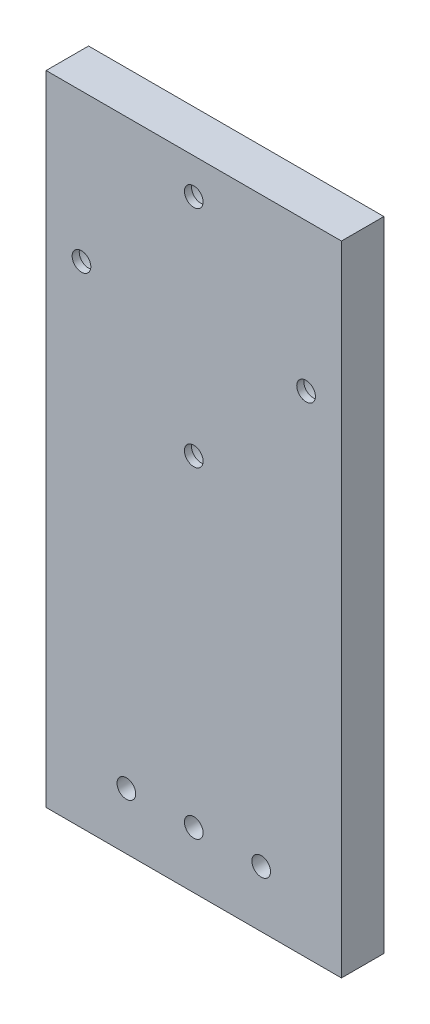
SolidWorks part; units mm, degrees
ref_plane "Front Plane" through (0, 0, 0) normal (0, 0, 1) x (1, 0, 0)
ref_plane "Top Plane" through (0, 0, 0) normal (0, 1, 0) x (1, 0, 0)
ref_plane "Right Plane" through (0, 0, 0) normal (1, 0, 0) x (0, 0, -1)
sketch "Sketch1" plane through (0, 0, 0) normal (0, 0, 1) x (1, 0, 0)
  line L0 (0, 0) -> (50000, 0) construction
  line L1 (0, 0) -> (0, -50000) construction
  line L2 (-9.53, -61.35) -> (49990.47, -61.35) construction
  line L4 (-20.875, 20.875) -> (20.875, 20.875)
  line L5 (-20.875, 20.875) -> (-20.875, -69.35)
  line L6 (-20.875, -69.35) -> (20.875, -69.35)
  line L7 (20.875, 20.875) -> (20.875, -69.35)
  line L13 (0, 9.53) -> (0, -4.4139) construction
  circle A0 centre (0, 0) radius 20 construction
  circle A1 centre (0, -15.875) radius 1.32
  circle A2 centre (-15.875, 0) radius 1.32
  circle A3 centre (0, 15.875) radius 1.32
  circle A4 centre (-9.53, -61.35) radius 1.32
  circle A5 centre (0, -61.35) radius 1.32
  circle A6 centre (9.53, -61.35) radius 1.32
  circle A7 centre (15.875, 0) radius 1.32
  point P19 (0, 0)
  point P24 (0, 0)
  dimension "D3" = 2.64
  dimension "D8" = 61.35
  dimension "D9" = 9.53
  dimension "D10" = 5
  dimension "D13" = 5
  dimension "D11" = 8
  dimension "D2" = 40
  dimension "D6" = 15.875
  dimension "D7" = 3
  dimension "D5" = 4
  dimension "D1" = 2.64
  dimension "D12" = 5
  dimension "D4" = 15.875
extrude "Boss-Extrude1" add sketch "Sketch1" along normal blind 6
sketch "Sketch2" plane through (0, 0, 0) normal (0, 0, -1) x (-1, 0, 0)
  circle A0 centre (-15.875, 0) radius 3.25
  circle A1 centre (0, 15.88) radius 3.25
  circle A2 centre (15.88, 0.005) radius 3.25
  circle A3 centre (0.005, -15.875) radius 3.25
  circle A4 centre (-15.875, 0) radius 1.32 construction
  point P12 (0.0025, 0.0025)
  dimension "D1" = 6.5
  dimension "D2" = 4
extrude "Cut-Extrude1" cut sketch "Sketch2" against normal blind 5
sketch "Sketch3" plane through (0, 0, 6) normal (0, 0, 1) x (1, 0, 0)
  circle A0 centre (0, 0) radius 15.875 construction
sketch "Sketch4" plane through (0, 0, 0) normal (0, 1, 0) x (1, 0, 0)
  line L0 (0, 0) -> (0, -18.0356) construction
equation "\"A\"=61.35"
equation "\"D8@Sketch1\"=\"A\""
